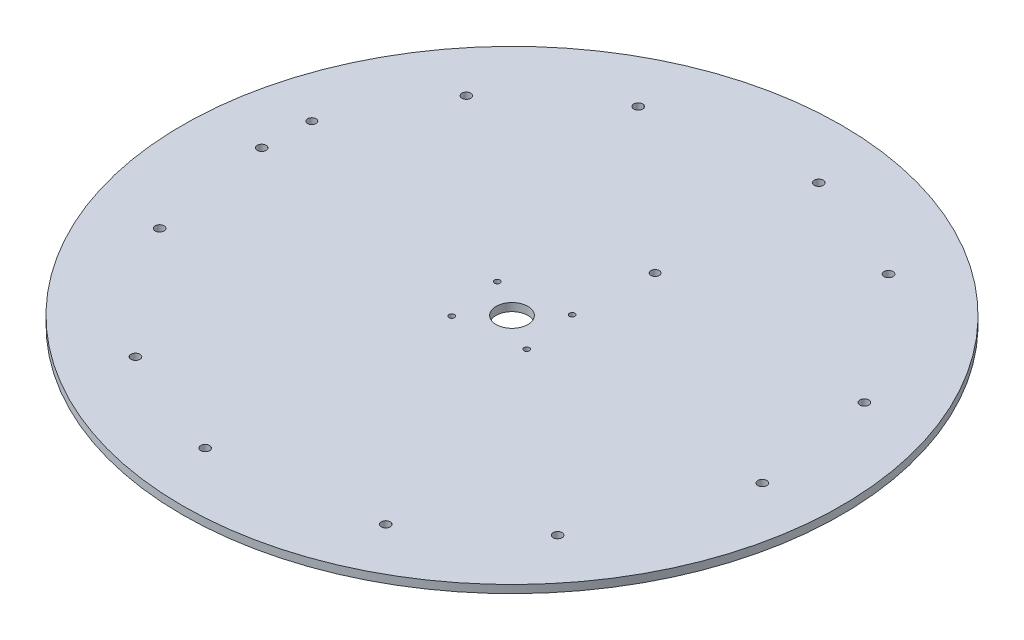
SolidWorks part; units mm, degrees
ref_plane "Front Plane" through (0, 0, 0) normal (0, 0, 1) x (1, 0, 0)
ref_plane "Top Plane" through (0, 0, 0) normal (0, 1, 0) x (1, 0, 0)
ref_plane "Right Plane" through (0, 0, 0) normal (1, 0, 0) x (0, 0, -1)
sketch "Sketch2" plane through (0, 0, 0) normal (0, 1, 0) x (1, 0, 0)
  circle A0 centre (0, 0) radius 125
  dimension "D1" = 250
extrude "Boss-Extrude1" add sketch "Sketch2" along normal blind 3
sketch "Sketch3" plane through (0, 3, 0) normal (0, 1, 0) x (1, 0, 0)
  line L4 (74.6446, 100.2656) -> (65.4599, 76.5843) construction
  line L5 (0, 0) -> (43.5629, 112.3204) construction
  line L6 (74.6446, 100.2656) -> (12.4813, 124.3753) construction
  line L7 (12.4813, 124.3753) -> (3.2966, 100.6941) construction
  line L8 (65.4599, 76.5843) -> (3.2966, 100.6941) construction
  circle A0 centre (0, 0) radius 125 construction
  circle A7 centre (57.8244, 84.9944) radius 1.7
  circle A8 centre (14.6061, 101.7564) radius 1.7
  circle A9 centre (44.6952, -92.5746) radius 1.7
  circle A10 centre (80.8206, -63.5274) radius 1.7
  circle A11 centre (-102.5195, 7.5802) radius 1.7
  circle A12 centre (-95.4267, -38.229) radius 1.7
  point P22 (0, 0)
  point P23 (0.4661, 0.2121)
  dimension "D2" = 3.4
  dimension "D1" = 25.4
  dimension "D3" = 5.08
  dimension "D5" = 66.675
  dimension "D6" = 3
  dimension "D4" = 10.16
extrude "Cut-Extrude1" cut sketch "Sketch3" against normal blind 26 and the other way blind 62
sketch "Sketch4" plane through (0, 3, 0) normal (0, 1, 0) x (1, 0, 0)
  circle A0 centre (0, 0) radius 6
  dimension "D1" = 12
extrude "Cut-Extrude2" cut sketch "Sketch4" against normal blind 12 and the other way blind 55
sketch "Sketch5" plane through (0, 0, 0) normal (0, -1, 0) x (1, 0, 0)
  circle A0 centre (-101.7781, -25.8548) radius 1.6
  circle A1 centre (13.2168, -41.0922) radius 1.6
  dimension "D1" = 3.2
  dimension "D2" = 3.2
extrude "Cut-Extrude3" cut sketch "Sketch5" against normal through all
sketch "Sketch6" plane through (0, 3, 0) normal (0, 1, 0) x (1, 0, 0)
  circle A0 centre (11.1984, 11.6251) radius 1.05
  circle A1 centre (13.8892, -8.3009) radius 1.05
  circle A2 centre (-11.1984, -11.6251) radius 1.05
  circle A3 centre (-13.8892, 8.3009) radius 1.05
extrude "Cut-Extrude4" cut sketch "Sketch6" against normal up to next
pattern_circular "CirPattern1" count 6 over 360 about axis through (0, 3, 0) along (0, 1, 0) of "Cut-Extrude1"
